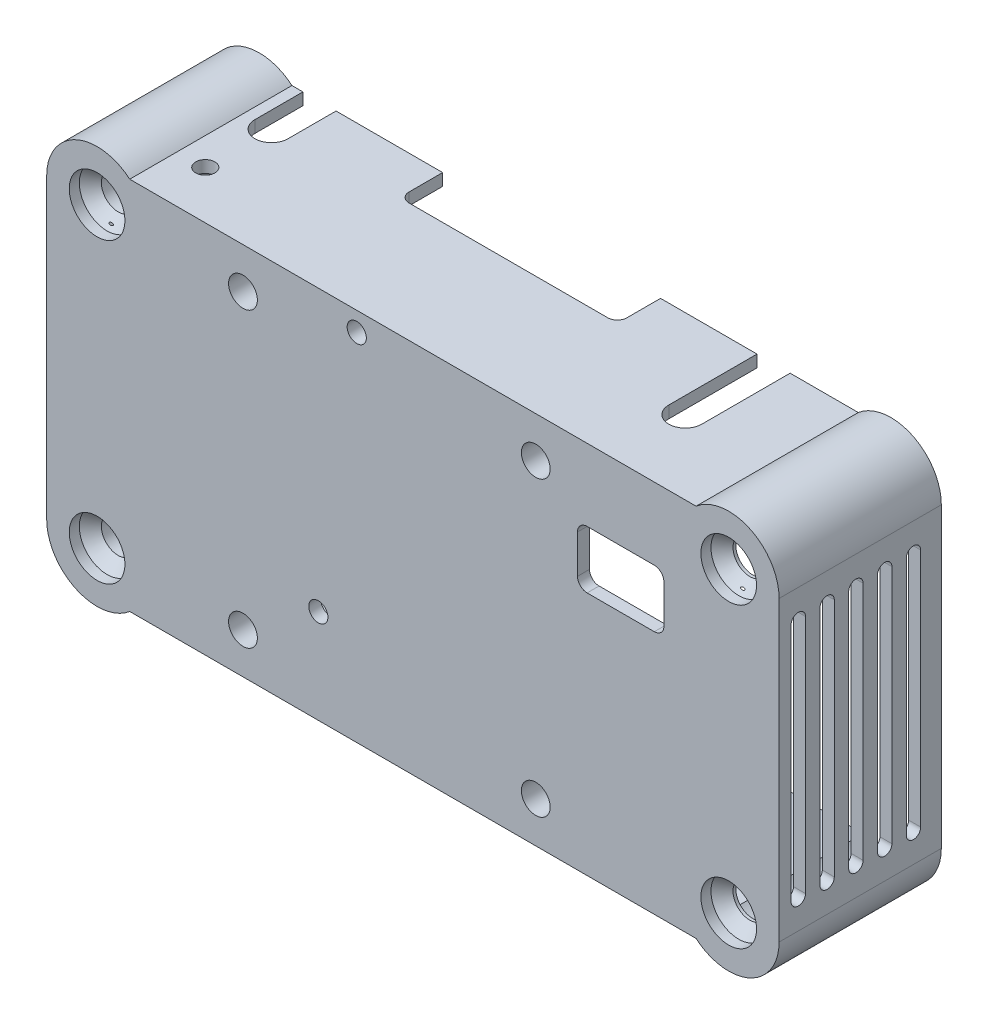
SolidWorks part; units mm, degrees
ref_plane "Front Plane" through (0, 0, 0) normal (0, 0, 1) x (1, 0, 0)
ref_plane "Top Plane" through (0, 0, 0) normal (0, 1, 0) x (1, 0, 0)
ref_plane "Right Plane" through (0, 0, 0) normal (1, 0, 0) x (0, 0, -1)
sketch "Sketch1" plane through (0, 0, 0) normal (0, 0, 1) x (1, 0, 0)
  line L0 (-29.7106, 19.8451) -> (30.4992, 19.8451)
  line L1 (-36.2557, 17.3451) -> (-36.2557, -13.6549)
  line L2 (-29.7106, -16.1549) -> (30.4992, -16.1549)
  line L3 (37.0443, 17.3451) -> (37.0443, -13.6549)
  circle A1 centre (-32.5057, 17.3451) radius 3.75
  arc A2 (-29.7106, 19.8451) -> (-36.2557, 17.3451) centre (-32.5057, 17.3451) ccw construction
  circle A3 centre (-32.5057, 17.3451) radius 1.75
  circle A4 centre (-32.5057, 17.3451) radius 1.75 construction
  circle A8 centre (-32.5057, -13.6549) radius 1.75
  circle A9 centre (-32.5057, -13.6549) radius 1.75 construction
  circle A10 centre (-32.5057, -13.6549) radius 3.75
  arc A11 (-36.2557, -13.6549) -> (-29.7106, -16.1549) centre (-32.5057, -13.6549) ccw construction
  circle A12 centre (33.2943, 17.3451) radius 3.75
  circle A14 centre (33.2943, 17.3451) radius 1.75
  circle A16 centre (33.2943, -13.6549) radius 3.75
  circle A18 centre (33.2943, -13.6549) radius 1.75
  circle A20 centre (33.2943, -13.6549) radius 1.75 construction
  circle A21 centre (33.2943, 17.3451) radius 1.75 construction
  arc A22 (37.0443, 17.3451) -> (30.1222, 15.3451) centre (33.2943, 17.3451) ccw construction
extrude "Boss-Extrude1" add sketch "Sketch1" along normal blind 2.5 contours A16 L3 A12 L0 A1 L1 A10 L2 | A1 A3 | A10 A8 | A12 A14 | A16 A18 region at (0.3943, 1.8451, 0) region at (-29.1016, 18.6453, 0) region at (34.5945, 20.7492, 0) region at (-32.5057, -10.011, 0) region at (34.5945, -17.059, 0)
sketch "Sketch2" plane through (0, 0, 2.5) normal (0, 0, 1) x (1, 0, 0)
  line L0 (-37.7557, 17.3451) -> (-37.7557, -13.6549)
  line L1 (-29.1053, -17.6549) -> (29.8939, -17.6549)
  line L2 (38.5443, -13.6549) -> (38.5443, 17.3451)
  line L3 (29.8939, 21.3451) -> (-29.1053, 21.3451)
  line L4 (-29.7106, -16.1549) -> (30.4992, -16.1549)
  line L5 (37.0443, -13.6549) -> (37.0443, 17.3451)
  line L6 (30.4992, 19.8451) -> (-29.7106, 19.8451)
  line L7 (-36.2557, 17.3451) -> (-36.2557, -13.6549)
  line L8 (-29.7106, -16.1549) -> (30.4992, -16.1549)
  line L9 (37.0443, -13.6549) -> (37.0443, 17.3451)
  line L10 (30.4992, 19.8451) -> (-29.7106, 19.8451)
  line L11 (-36.2557, 17.3451) -> (-36.2557, -13.6549)
  arc A0 (-29.1053, 21.3451) -> (-37.7557, 17.3451) centre (-32.5057, 17.3451) ccw
  arc A1 (-37.7557, -13.6549) -> (-29.1053, -17.6549) centre (-32.5057, -13.6549) ccw
  arc A2 (29.8939, -17.6549) -> (38.5443, -13.6549) centre (33.2943, -13.6549) ccw
  arc A3 (38.5443, 17.3451) -> (29.8939, 21.3451) centre (33.2943, 17.3451) ccw
  arc A4 (30.4992, -16.1549) -> (37.0443, -13.6549) centre (33.2943, -13.6549) ccw
  arc A5 (37.0443, 17.3451) -> (30.4992, 19.8451) centre (33.2943, 17.3451) ccw
  arc A6 (-29.7106, 19.8451) -> (-36.2557, 17.3451) centre (-32.5057, 17.3451) ccw
  arc A7 (-36.2557, -13.6549) -> (-29.7106, -16.1549) centre (-32.5057, -13.6549) ccw
  arc A8 (30.4992, -16.1549) -> (37.0443, -13.6549) centre (33.2943, -13.6549) ccw
  arc A9 (37.0443, 17.3451) -> (30.4992, 19.8451) centre (33.2943, 17.3451) ccw
  arc A10 (-29.7106, 19.8451) -> (-36.2557, 17.3451) centre (-32.5057, 17.3451) ccw
  arc A11 (-36.2557, -13.6549) -> (-29.7106, -16.1549) centre (-32.5057, -13.6549) ccw
  dimension "D1" = 0
  dimension "D2" = 1.5
extrude "Boss-Extrude2" add sketch "Sketch2" against normal up to surface (2.5 mm away) up to face at (0.3943, 1.8451, 0)
sketch "Sketch3" plane through (0, 0, 0) normal (0, 0, -1) x (-1, 0, 0)
  line L1 (29.601, 20.0951) -> (-30.3896, 20.0951)
  line L2 (-37.2943, 17.3451) -> (-37.2943, -13.6549)
  line L3 (-30.3896, -16.4049) -> (29.601, -16.4049)
  line L4 (29.1053, 21.3451) -> (-29.8939, 21.3451)
  line L5 (-38.5443, 17.3451) -> (-38.5443, -13.6549)
  line L6 (-29.8939, -17.6549) -> (29.1053, -17.6549)
  line L7 (37.7557, -13.6549) -> (37.7557, 17.3451)
  line L8 (29.1053, 21.3451) -> (-29.8939, 21.3451)
  line L9 (-38.5443, 17.3451) -> (-38.5443, -13.6549)
  line L10 (-29.8939, -17.6549) -> (29.1053, -17.6549)
  line L11 (37.7557, -13.6549) -> (37.7557, 17.3451)
  line L12 (36.5057, -13.6549) -> (36.5057, 17.3451)
  arc A1 (-30.3896, 20.0951) -> (-37.2943, 17.3451) centre (-33.2943, 17.3451) ccw
  arc A2 (-37.2943, -13.6549) -> (-30.3896, -16.4049) centre (-33.2943, -13.6549) ccw
  arc A3 (29.601, -16.4049) -> (36.5057, -13.6549) centre (32.5057, -13.6549) ccw
  arc A4 (37.7557, 17.3451) -> (29.1053, 21.3451) centre (32.5057, 17.3451) ccw
  arc A5 (-29.8939, 21.3451) -> (-38.5443, 17.3451) centre (-33.2943, 17.3451) ccw
  arc A6 (-38.5443, -13.6549) -> (-29.8939, -17.6549) centre (-33.2943, -13.6549) ccw
  arc A7 (29.1053, -17.6549) -> (37.7557, -13.6549) centre (32.5057, -13.6549) ccw
  arc A8 (37.7557, 17.3451) -> (29.1053, 21.3451) centre (32.5057, 17.3451) ccw
  arc A9 (-29.8939, 21.3451) -> (-38.5443, 17.3451) centre (-33.2943, 17.3451) ccw
  arc A10 (-38.5443, -13.6549) -> (-29.8939, -17.6549) centre (-33.2943, -13.6549) ccw
  arc A11 (29.1053, -17.6549) -> (37.7557, -13.6549) centre (32.5057, -13.6549) ccw
  arc A12 (36.5057, 17.3451) -> (29.601, 20.0951) centre (32.5057, 17.3451) ccw
  dimension "D1" = 0
  dimension "D2" = 1.25
extrude "Boss-Extrude3" add sketch "Sketch3" along normal up to surface (14.4 mm away)
sketch "Sketch8" plane through (0, 0, 0) normal (0, 0, -1) x (-1, 0, 0)
  line L0 (37.7557, 17.3451) -> (37.7557, -13.6549)
  line L1 (29.1053, 21.3451) -> (29.1053, -17.6549)
  circle A0 centre (32.5057, 17.3451) radius 5.25
  arc A1 (37.7557, 17.3451) -> (29.1053, 21.3451) centre (32.5057, 17.3451) ccw construction
  circle A2 centre (32.5057, 17.3451) radius 1.75
  circle A3 centre (32.5057, 17.3451) radius 1.75 construction
  circle A4 centre (32.5057, -13.6549) radius 5.25
  arc A5 (29.1053, -17.6549) -> (37.7557, -13.6549) centre (32.5057, -13.6549) ccw construction
  circle A6 centre (32.5057, -13.6549) radius 1.75
  circle A7 centre (32.5057, -13.6549) radius 1.75 construction
  circle M3 centre (32.5057, 17.3451) radius 1.75
  circle M4 centre (32.5057, -13.6549) radius 1.75
  arc M5 (29.601, -16.4049) -> (36.5057, -13.6549) centre (32.5057, -13.6549) ccw
  line M6 (36.5057, -13.6549) -> (36.5057, 17.3451)
  arc M7 (36.5057, 17.3451) -> (29.601, 20.0951) centre (32.5057, 17.3451) ccw
  line M8 (29.601, 20.0951) -> (-30.3896, 20.0951)
  line M12 (-30.3896, -16.4049) -> (29.601, -16.4049)
extrude "Boss-Extrude4" add sketch "Sketch8" along normal up to surface (6.75 mm away) contours L1 A0 M6 M7 M8 M3 | A4 A0 L1 M6 | A4 L1 M6 M12 M5 M4 region at (-32.835, 1.8451, 0) region at (-32.9201, 12.2303, 0) region at (-36.3872, -11.9547, 0)
sketch "Sketch4" plane through (-37.7557, 0, 0) normal (-1, 0, 0) x (0, 0, 1)
  line L12 (-11.9, -11.8549) -> (-3.3, -11.8549)
  line L13 (-3.3, -11.8549) -> (-3.3, 1.2216)
  line L14 (-3.3, 1.2216) -> (-6.0107, 4.2451)
  line L15 (-6.0107, 4.2451) -> (-9.1893, 4.2451)
  line L16 (-9.1893, 4.2451) -> (-11.9, 1.2216)
  line L17 (-11.9, 1.2216) -> (-11.9, -11.8549)
  line L18 (-11.9, -11.8549) -> (-3.3, -11.8549)
  line L19 (-3.3, -11.8549) -> (-3.3, 1.2216)
  line L20 (-3.3, 1.2216) -> (-6.0107, 4.2451)
  line L21 (-6.0107, 4.2451) -> (-9.1893, 4.2451)
  line L22 (-9.1893, 4.2451) -> (-11.9, 1.2216)
  line L23 (-11.9, 1.2216) -> (-11.9, -11.8549)
  dimension "D1" = 0.2
extrude "Cut-Extrude1" cut sketch "Sketch4" against normal up to next
sketch "Sketch5" plane through (0, 21.3451, 0) normal (0, 1, 0) x (1, 0, 0)
  line L0 (-27.9607, 9.4) -> (-27.9607, 14.4)
  line L1 (-29.1053, 14.4) -> (29.8939, 14.4) construction
  line L2 (-24.5107, 9.4) -> (-24.5107, 14.4)
  line L3 (-24.5107, 14.4) -> (-27.9607, 14.4)
  line L4 (19.3445, 5.2047) -> (19.3445, 14.4)
  line L5 (22.7945, 5.2047) -> (22.7945, 14.4)
  circle A1 centre (21.0695, 5.2047) radius 1.725
  circle A2 centre (-26.2357, 9.4) radius 1.725
  circle A3 centre (-26.2357, 9.4) radius 1.725
  circle A4 centre (21.0695, 5.2047) radius 0.95 construction
  line M3 (29.8939, 14.4) -> (-29.1053, 14.4)
  dimension "D1" = 0.5
extrude "Cut-Extrude2" cut sketch "Sketch5" against normal up to next contours A3 | A3 L2 L0 M3 | A1 L5 L4 M3 | A1 region at (21.0695, 21.3451, -10.4703) region at (-26.2357, 21.3451, -12.5571) region at (-26.2357, 21.3451, -9.4) region at (21.0695, 21.3451, -5.2047)
sketch "Sketch6" plane through (0, 21.3451, 0) normal (0, 1, 0) x (1, 0, 0)
  line L0 (-26.2357, 7.675) -> (-26.2357, -2.5) construction
  line L1 (29.8939, -2.5) -> (-29.1053, -2.5) construction
  arc A0 (-27.9607, 9.4) -> (-24.5107, 9.4) centre (-26.2357, 9.4) ccw construction
  circle A1 centre (-26.2357, 2.5) radius 1
  dimension "D1" = 2
  dimension "D2" = 5
extrude "Cut-Extrude3" cut sketch "Sketch6" against normal through all
sketch "Sketch7" plane through (0, 0, 2.5) normal (0, 0, 1) x (1, 0, 0)
  line L1 (26.5443, 7.8451) -> (17.5443, 7.8451)
  line L2 (26.5443, 7.8451) -> (26.5443, 13.8451)
  line L3 (26.5443, 13.8451) -> (17.5443, 13.8451)
  line L4 (17.5443, 7.8451) -> (17.5443, 13.8451)
  line L6 (38.5443, -13.6549) -> (38.5443, 17.3451) construction
  line L7 (29.8939, 21.3451) -> (-29.1053, 21.3451) construction
  line L8 (-3.2057, 19.3451) -> (-3.2057, 21.3451) construction
  line L9 (-7.7057, 19.3451) -> (-7.7057, 21.3451) construction
  line L10 (-3.2057, 18.0451) -> (-3.2057, 19.8451) construction
  line L11 (-7.7057, 18.0451) -> (-7.7057, 19.8451) construction
  circle A0 centre (-9.4557, -7.8549) radius 1
  circle A1 centre (-5.4557, 19.3451) radius 2.25
  circle A2 centre (-9.4557, -7.8549) radius 0.875 construction
  circle A3 centre (-5.4557, 19.3451) radius 1
  dimension "D5" = 2
  dimension "D6" = 2
  dimension "D1" = 12
  dimension "D2" = 7.5
  dimension "D3" = 6
  dimension "D4" = 9
extrude "Cut-Extrude4" cut sketch "Sketch7" against normal up to next contours L4 L1 L2 L3 | A3 | A0 region at (22.0443, 10.8451, 2.5) region at (-9.4557, -7.8549, 2.5) region at (-5.4557, 19.3451, 2.5)
sketch "Sketch9" plane through (0, 0, 2.5) normal (0, 0, 1) x (1, 0, 0)
  circle A0 centre (-32.5057, 17.3451) radius 2.9
  circle A1 centre (33.2943, 17.3451) radius 2.9
  circle A2 centre (33.2943, -13.6549) radius 2.9
  circle A3 centre (-32.5057, -13.6549) radius 2.9
  dimension "D1" = 5.8
extrude "Cut-Extrude5" cut sketch "Sketch9" against normal blind 0.2
chamfer "Chamfer1" distance 2 angle 45 4 edges at (35.0443, -13.6549, 2.3) (35.0443, 17.3451, 2.3) (-30.7557, -13.6549, 2.3) (-30.7557, 17.3451, 2.3)
sketch "Sketch10" plane through (0, 21.3451, 0) normal (0, 1, 0) x (1, 0, 0)
  line L0 (-24.5107, 14.4) -> (19.3445, 14.4) construction
  line L1 (9.2943, 14.4) -> (4.6943, 14.4)
  line L2 (9.2943, 14.4) -> (9.2943, 9.9)
  line L3 (9.2943, 9.9) -> (4.6943, 9.9)
  line L4 (4.6943, 14.4) -> (4.6943, 9.9)
  line L5 (9.2943, 13.7) -> (9.2943, 11.9) construction
  line L6 (4.6943, 13.7) -> (4.6943, 11.9) construction
  line L7 (-8.8057, 13.7) -> (-8.8057, 11.9) construction
  line L8 (-8.8057, 14.4) -> (-13.4057, 14.4)
  line L9 (-8.8057, 14.4) -> (-8.8057, 9.9)
  line L10 (-8.8057, 9.9) -> (-13.4057, 9.9)
  line L11 (-13.4057, 14.4) -> (-13.4057, 9.9)
  line L12 (-13.4057, 13.7) -> (-13.4057, 11.9) construction
  line L14 (-8.8057, 14.4) -> (4.6943, 14.4)
  line L15 (-8.8057, 14.4) -> (-8.8057, 9.9)
  line L16 (-8.8057, 9.9) -> (4.6943, 9.9)
  line L17 (4.6943, 14.4) -> (4.6943, 9.9)
  line M23 (19.3445, 14.4) -> (-24.5107, 14.4)
  dimension "D1" = 4.5
extrude "Cut-Extrude6" cut sketch "Sketch10" against normal through all contours L11 L10 L9 M23 | L9 L16 L4 M23 | L4 L3 L2 M23 region at (6.9943, 21.3451, -12.15) region at (-2.0557, 21.3451, -12.15) region at (-11.1057, 21.3451, -12.15)
fillet "Fillet1" radius 1 8 edges at (26.5443, 13.8451, 1.25) (26.5443, 7.8451, 1.25) (17.5443, 7.8451, 1.25) (17.5443, 13.8451, 1.25) (9.2943, 20.7201, -9.9) (9.2943, -17.0299, -9.9) (-13.4057, -17.0299, -9.9) (-13.4057, 20.7201, -9.9)
sketch "Sketch11" plane through (0, 0, -3.3) normal (0, 0, -1) x (-1, 0, 0)
  line L0 (29.1053, -5.3166) -> (36.5057, -5.3166) construction
  line L1 (29.1053, 1.2216) -> (29.1053, -11.8549) construction
  line L2 (36.5057, -13.6549) -> (36.5057, 17.3451) construction
  line L3 (29.1053, 1.2216) -> (37.7557, 1.2216) construction
  line L4 (32.5555, 1.2216) -> (33.0555, 1.2216)
  line L5 (32.5555, 1.2216) -> (32.5555, -11.8549)
  line L6 (32.5555, -11.8549) -> (33.0555, -11.8549)
  line L7 (33.0555, 1.2216) -> (33.0555, -11.8549)
  line L8 (32.5555, 1.2216) -> (33.0555, -11.8549) construction
  line L9 (32.5555, -11.8549) -> (33.0555, 1.2216) construction
  point P6 (32.8055, -5.3166)
  dimension "D1" = 0.5
extrude "Boss-Extrude5" add sketch "Sketch11" along normal blind 0.25
sketch "Sketch12" plane through (0, 0, 2.5) normal (0, 0, 1) x (1, 0, 0)
  circle A0 centre (-17.3057, 17.0951) radius 1.5
  circle A1 centre (13.1943, 17.0951) radius 1.5
  circle A2 centre (13.1943, -13.4049) radius 1.5
  circle A3 centre (-17.3057, -13.4049) radius 1.5
  circle A4 centre (-17.3057, 17.0951) radius 1.5 construction
  circle A5 centre (-17.3057, -13.4049) radius 1.5 construction
  circle A6 centre (13.1943, -13.4049) radius 1.5 construction
  circle A7 centre (13.1943, 17.0951) radius 1.5 construction
  dimension "D1" = 3
extrude "Cut-Extrude7" cut sketch "Sketch12" against normal up to next
sketch "Sketch13" plane through (38.5443, 0, 0) normal (1, 0, 0) x (0, 0, -1)
  line L0 (-0.5, 22.5951) -> (-0.5, -18.9049) construction
  line L1 (14.4, 22.5951) -> (-2.5, 22.5951) construction
  line L2 (-2.5, -18.9049) -> (14.4, -18.9049) construction
  line L3 (-2.5, 22.5951) -> (-2.5, 17.3451) construction
  line L4 (-2.5, 1.8451) -> (14.4, 1.8451) construction
  line L5 (-2.5, -13.6549) -> (-2.5, 17.3451) construction
  line L6 (14.4, 17.3451) -> (14.4, -13.6549) construction
  line L7 (-0.5, 14.3451) -> (-0.5, -10.6549) construction
  line L8 (0.25, 14.3451) -> (0.25, -10.6549)
  line L9 (-1.25, 14.3451) -> (-1.25, -10.6549)
  line L10 (2.5, 14.3451) -> (2.5, -10.6549) construction
  line L11 (3.25, 14.3451) -> (3.25, -10.6549)
  line L12 (1.75, 14.3451) -> (1.75, -10.6549)
  line L13 (5.5, 14.3451) -> (5.5, -10.6549) construction
  line L14 (6.25, 14.3451) -> (6.25, -10.6549)
  line L15 (4.75, 14.3451) -> (4.75, -10.6549)
  line L16 (8.5, 14.3451) -> (8.5, -10.6549) construction
  line L17 (9.25, 14.3451) -> (9.25, -10.6549)
  line L18 (7.75, 14.3451) -> (7.75, -10.6549)
  line L19 (11.5, 14.3451) -> (11.5, -10.6549) construction
  line L20 (12.25, 14.3451) -> (12.25, -10.6549)
  line L21 (10.75, 14.3451) -> (10.75, -10.6549)
  arc A0 (0.25, 14.3451) -> (-1.25, 14.3451) centre (-0.5, 14.3451) ccw
  arc A1 (-1.25, -10.6549) -> (0.25, -10.6549) centre (-0.5, -10.6549) ccw
  arc A2 (3.25, 14.3451) -> (1.75, 14.3451) centre (2.5, 14.3451) ccw
  arc A3 (1.75, -10.6549) -> (3.25, -10.6549) centre (2.5, -10.6549) ccw
  arc A4 (6.25, 14.3451) -> (4.75, 14.3451) centre (5.5, 14.3451) ccw
  arc A5 (4.75, -10.6549) -> (6.25, -10.6549) centre (5.5, -10.6549) ccw
  arc A6 (9.25, 14.3451) -> (7.75, 14.3451) centre (8.5, 14.3451) ccw
  arc A7 (7.75, -10.6549) -> (9.25, -10.6549) centre (8.5, -10.6549) ccw
  arc A8 (12.25, 14.3451) -> (10.75, 14.3451) centre (11.5, 14.3451) ccw
  arc A9 (10.75, -10.6549) -> (12.25, -10.6549) centre (11.5, -10.6549) ccw
  point P17 (-0.5, 1.8451)
  point P25 (2.5, 1.8451)
  point P32 (5.5, 1.8451)
  point P39 (8.5, 1.8451)
  point P46 (11.5, 1.8451)
  dimension "D1" = 2
  dimension "D2" = 25
  dimension "D3" = 1.5
  dimension "D5" = 3
  dimension "D4" = 5
extrude "Cut-Extrude8" cut sketch "Sketch13" against normal up to next
